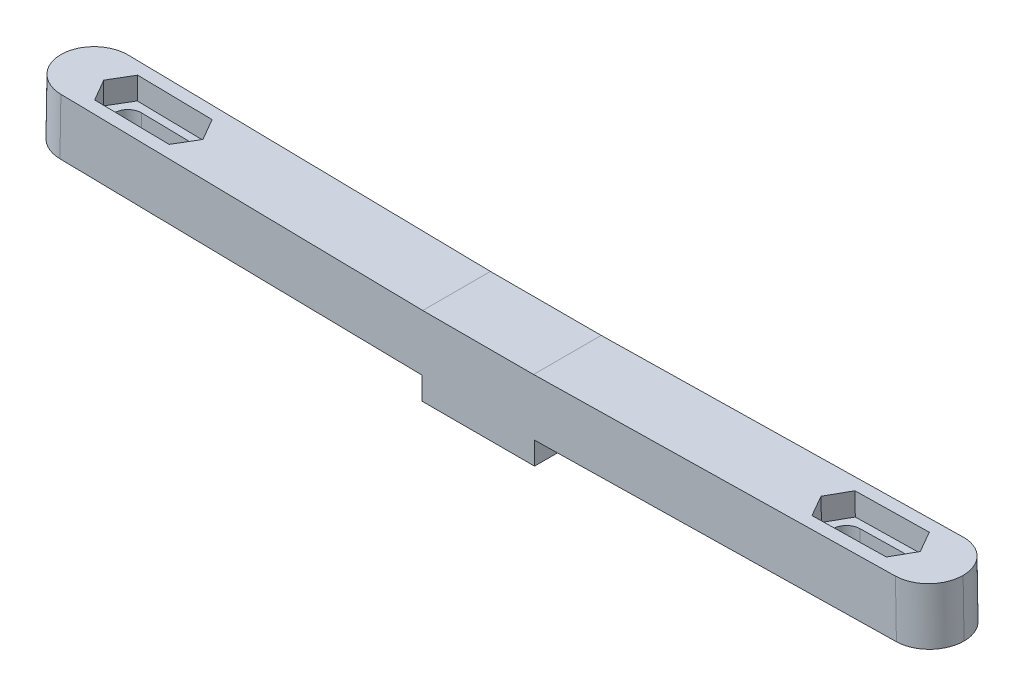
SolidWorks part; units mm, degrees
ref_plane "Front Plane" through (0, 0, 0) normal (0, 0, 1) x (1, 0, 0)
ref_plane "Top Plane" through (0, 0, 0) normal (0, 1, 0) x (1, 0, 0)
ref_plane "Right Plane" through (0, 0, 0) normal (1, 0, 0) x (0, 0, -1)
sketch "Sketch1" plane through (0, 0, 0) normal (0, 0, 1) x (1, 0, 0)
  line L1 (10, 0) -> (45.0873, 0.6125)
  line L2 (45.0873, 0.6125) -> (45, 5.6117)
  line L3 (45, 5.6117) -> (9.9127, 4.9992)
  line L4 (9.9127, 4.9992) -> (0.0873, 4.9992)
  line L5 (0.0873, 4.9992) -> (-35, 5.6117)
  line L6 (-35, 5.6117) -> (-35.0873, 0.6125)
  line L7 (-35.0873, 0.6125) -> (0, 0)
  line L8 (0, 0) -> (0, -2)
  line L9 (0, -2) -> (10, -2)
  line L10 (10, -2) -> (10, 0)
  dimension "D1" = 1
  dimension "D2" = 10
  dimension "D3" = 5
  dimension "D4" = 80
  dimension "D5" = 2
extrude "Boss-Extrude1" add sketch "Sketch1" along normal blind 6
sketch "Sketch2" plane through (0.0873, 4.9992, 0) normal (0.0175, 0.9998, 0) x (0.9998, -0.0175, 0)
  line L3 (-29.0926, -3) -> (-24.6926, -3) construction
  line L4 (-29.0926, -1.8) -> (-24.6926, -1.8)
  line L5 (-29.0926, -4.2) -> (-24.6926, -4.2)
  line L6 (0, 0) -> (-35.0926, 0) construction
  line L8 (-30.1926, -1.0947) -> (-31.2926, -3)
  line L9 (-31.2926, -3) -> (-30.1926, -4.9053)
  line L10 (-30.1926, -4.9053) -> (-23.5926, -4.9053)
  line L11 (-23.5926, -4.9053) -> (-22.4926, -3)
  line L12 (-22.4926, -3) -> (-23.5926, -1.0947)
  line L13 (-23.5926, -1.0947) -> (-30.1926, -1.0947)
  line L14 (-27.9926, -1.0947) -> (-26.8926, -3) construction
  line L15 (-26.8926, -3) -> (-27.9926, -4.9053) construction
  line L16 (-31.2926, -3) -> (-29.0926, -3) construction
  line L17 (-24.6926, -3) -> (-22.4926, -3) construction
  line L18 (-30.1926, -1.0947) -> (-29.0926, -3) construction
  line L19 (-29.0926, -3) -> (-27.9926, -1.0947) construction
  line L20 (-35.0926, -6) -> (-35.0926, 0) construction
  arc A1 (-29.0926, -1.8) -> (-29.0926, -4.2) centre (-29.0926, -3) ccw
  arc A2 (-24.6926, -4.2) -> (-24.6926, -1.8) centre (-24.6926, -3) ccw
  point P2 (-26.8926, -3)
  dimension "D1" = 3
  dimension "D2" = 6
  dimension "D4" = 1.2
  dimension "D5" = 2.2
  dimension "D6" = 2.2
  dimension "D7" = 120
extrude "Cut-Extrude1" cut sketch "Sketch2" against normal blind 6 contours L5 A2 L4 A1 region at (-26.8012, 5.4686, 3)
extrude "Cut-Extrude3" cut sketch "Sketch2<3>" against normal blind 2 contours L12 L13 L8 L9 L10 L11 A2 L5 A1 L4 region at (-26.8012, 5.4686, 1.1906)
sketch "Sketch2<3>" plane through (0.0873, 4.9992, 0) normal (0.0175, 0.9998, 0) x (0.9998, -0.0175, 0) same geometry as "Sketch2"
ref_plane "Plane1" through (5, 0, 0) normal (1, 0, 0) x (0, 0, -1)
mirror "Mirror1" about plane through (5, 0, 0) normal (1, 0, 0) of "Cut-Extrude1", "Cut-Extrude3"
fillet "Fillet1" radius 3 4 edges at (45.0436, 3.1121, 0) (45.0436, 3.1121, 6) (-35.0436, 3.1121, 0) (-35.0436, 3.1121, 6)
